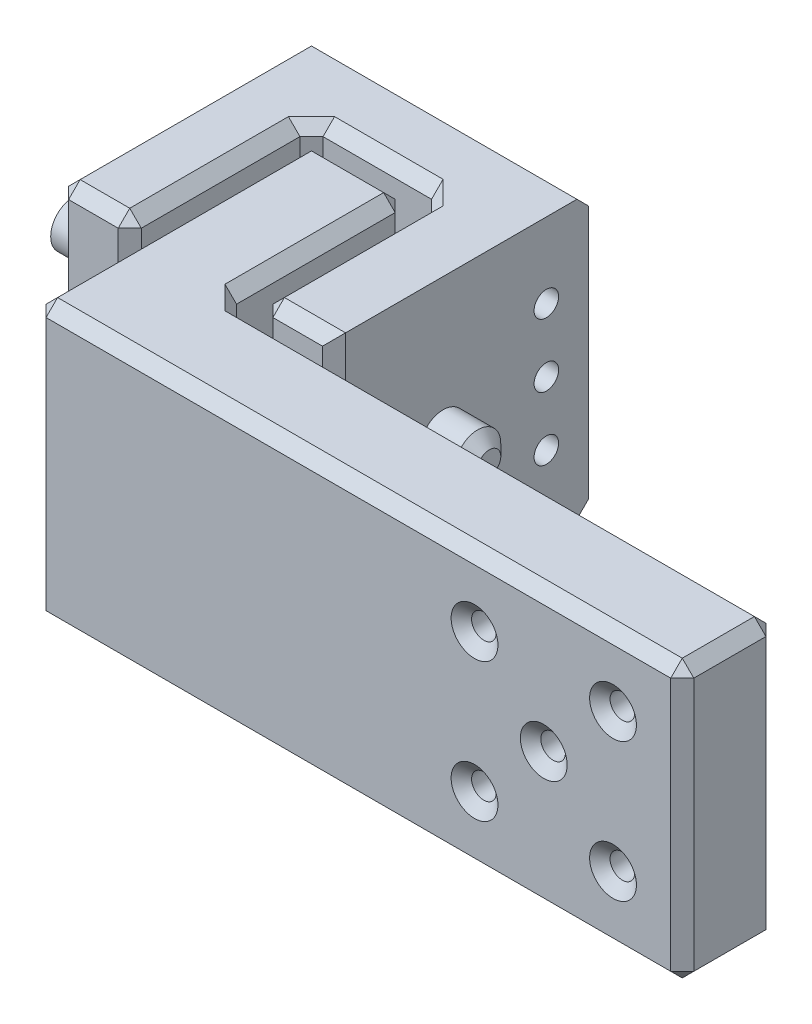
SolidWorks part; units mm, degrees
note: The reader was unsure of these and kept them because the rebuilt part matched: shared geometry of "Sketch7<2>".
ref_plane "Front Plane" through (0, 0, 0) normal (0, 0, 1) x (1, 0, 0)
ref_plane "Top Plane" through (0, 0, 0) normal (0, 1, 0) x (1, 0, 0)
ref_plane "Right Plane" through (0, 0, 0) normal (1, 0, 0) x (0, 0, -1)
sketch "Sketch1" plane through (0, 0, 0) normal (0, 1, 0) x (1, 0, 0)
  line L0 (0, 0) -> (0, 50)
  line L1 (0, 50) -> (36.2, 50)
  line L2 (36.2, 50) -> (36.2, 0)
  line L3 (36.2, 0) -> (56.2, 0)
  line L4 (56.2, 0) -> (56.2, 70)
  line L5 (56.2, 70) -> (-20, 70)
  line L6 (-20, 70) -> (-20, 0)
  line L7 (-20, 0) -> (0, 0)
  line L8 (31.2, 45) -> (5, 45)
  line L9 (5, 45) -> (5, -31.2)
  line L10 (5, -31.2) -> (183.2, -31.2)
  line L11 (183.2, -31.2) -> (183.2, -5)
  line L12 (183.2, -5) -> (31.2, -5)
  line L13 (31.2, -5) -> (31.2, 45)
  dimension "D1" = 5
  dimension "D2" = 5
  dimension "D3" = 5
  dimension "D4" = 5
  dimension "D5" = 20
  dimension "D6" = 20
  dimension "D7" = 20
  dimension "D8" = 76.2
  dimension "D9" = 76.2
  dimension "D10" = 127
extrude "Boss-Extrude1" add sketch "Sketch1" along normal blind 76.2
ref_plane "Plane1" through (0, 0, -45) normal (0, 0, -1) x (-1, 0, 0)
ref_plane "Plane2" through (0, 0, 0) normal (0, 0, 1) x (1, 0, 0)
sketch "Sketch3" plane through (-20, 0, 0) normal (-1, 0, 0) x (0, 0, 1)
  line L0 (0, 38.1) -> (-70, 38.1) construction
  line L3 (0, 76.2) -> (0, 0) construction
  line L6 (-70, 76.2) -> (-70, 0) construction
  line L8 (-45, 76.2) -> (-45, 0) construction
  circle A0 centre (-30, 38.1) radius 6.35
  point P7 (0, 0)
  point P8 (0, 0)
  point P9 (0, 0)
  point P10 (0, 0)
  dimension "D1" = 12.7
  dimension "D2" = 15
extrude "Cut-Extrude1" cut sketch "Sketch3" against normal through all both and the other way through all contours A0
chamfer "Chamfer1" distance 6.35 angle 45 1 edges at (-20, 38.1, -36.35)
chamfer "Chamfer2" distance 3.175 angle 45 20 edges at (31.2, 38.1, -23.65) (5, 38.1, -36.35) (183.2, 38.1, 5) (183.2, 76.2, 18.1) (183.2, 38.1, 31.2) (183.2, 0, 18.1) (18.1, 0, -45) (31.2, 0, -20) (107.2, 0, 5) (31.2, 38.1, 5) (94.1, 0, 31.2) (5, 0, -6.9) (5, 38.1, 31.2) (94.1, 76.2, 31.2) (5, 76.2, -6.9) (107.2, 76.2, 5) (31.2, 76.2, -20) (31.2, 38.1, -45) (18.1, 76.2, -45) (5, 38.1, -45)
chamfer "Chamfer3" distance 3.175 angle 45 1 edges at (36.2, 38.1, -36.35)
chamfer "Chamfer4" distance 3.175 angle 45 23 edges at (18.1, 0, -50) (46.2, 76.2, 0) (56.2, 76.2, -35) (56.2, 38.1, 0) (56.2, 0, -35) (46.2, 0, 0) (36.2, 0, -25) (36.2, 38.1, 0) (0, 38.1, -50) (-20, 38.1, -70) (-20, 0, -35) (0, 0, -25) (-10, 0, 0) (0, 38.1, 0) (-20, 38.1, 0) (36.2, 76.2, -25) (18.1, 76.2, -50) (0, 76.2, -25) (-10, 76.2, 0) (-20, 76.2, -35) (36.2, 38.1, -50) (18.1, 0, -70) (18.1, 76.2, -70)
sketch "Sketch4" plane through (0, 0, 31.2) normal (0, 0, 1) x (1, 0, 0)
  line L0 (180.025, 73.025) -> (8.175, 73.025) construction
  line L1 (110.175, 3.175) -> (180.025, 3.175) construction
  line L2 (110.175, 3.175) -> (110.175, 73.025) construction
  line L3 (110.175, 73.025) -> (180.025, 73.025) construction
  line L4 (180.025, 3.175) -> (180.025, 73.025) construction
  line L5 (110.175, 3.175) -> (180.025, 73.025) construction
  line L6 (110.175, 73.025) -> (180.025, 3.175) construction
  line L7 (180.025, 3.175) -> (180.025, 73.025) construction
  line L8 (8.175, 3.175) -> (180.025, 3.175) construction
  line L10 (126.05, 19.05) -> (164.15, 19.05) construction
  line L11 (126.05, 19.05) -> (126.05, 57.15) construction
  line L12 (126.05, 57.15) -> (164.15, 57.15) construction
  line L13 (164.15, 19.05) -> (164.15, 57.15) construction
  line L14 (126.05, 19.05) -> (164.15, 57.15) construction
  line L15 (126.05, 57.15) -> (164.15, 19.05) construction
  point P0 (145.1, 38.1)
  point P11 (145.1, 38.1)
  point P17 (126.05, 57.15)
  point P18 (164.15, 57.15)
  point P19 (164.15, 19.05)
  point P20 (126.05, 19.05)
  dimension "D1" = 38.1
hole_wizard "CSK for 1/4 Flat Head Machine Screw (100)1" positions "Sketch4" profile "Sketch6" countersink size "1/4" standard "ANSI Inch"
sketch "Sketch6" plane through (126.05, 19.05, 31.2) normal (1, 0, 0) x (0, -1, 0)
  line L0 (0, 0) -> (0, 28.2298)
  line L1 (0, 28.2298) -> (3.3782, 26.2)
  line L2 (3.3782, 26.2) -> (3.3782, 2.5682)
  line L3 (3.3782, 2.5682) -> (6.4389, 0)
  line L5 (6.4389, 0) -> (0, 0)
  line L6 (-3.3782, 2.5682) -> (-6.4389, 0) construction
  line L10 (0, 28.2298) -> (-3.3782, 26.2) construction
  line L11 (0, -6.35) -> (0, 107.95) construction
  dimension "Hole Dia." = 6.7564
  dimension "Hole Depth" = 26.2
  dimension "Near C'Sink Dia." = 12.8778
  dimension "Near C'Sink Angle" = 100
  dimension "Drill Angle" = 118
sketch "Sketch7" plane through (-20, 0, 0) normal (-1, 0, 0) x (0, 0, 1)
  circle A0 centre (-30, 38.1) radius 6.35
  circle A1 centre (-30, 38.1) radius 6.35 construction
extrude "Boss-Extrude2" add sketch "Sketch7" against normal blind 88.9 separate body
extrude "Boss-Extrude3" add sketch "Sketch7<2>" along normal blind 25.4
sketch "Sketch7<2>" plane through (-20, 0, 0) normal (-1, 0, 0) x (0, 0, 1) same geometry as "Sketch7"
sketch "Sketch8" plane through (-20, 0, 0) normal (-1, 0, 0) x (0, 0, 1)
  line L0 (-66.825, 3.175) -> (-3.175, 3.175) construction
  line L1 (-66.825, 73.025) -> (-50, 73.025) construction
  line L2 (-66.825, 73.025) -> (-66.825, 3.175) construction
  line L3 (-66.825, 3.175) -> (-50, 3.175) construction
  line L4 (-50, 73.025) -> (-50, 3.175) construction
  line L5 (-50, 73.025) -> (-50, 3.175) construction
  line L7 (-58.4125, 38.1) -> (-58.4125, 20.6375) construction
  line L8 (-58.4125, 20.6375) -> (-58.4125, 3.175) construction
  line L9 (-58.4125, 38.1) -> (-58.4125, 55.5625) construction
  line L11 (-58.4125, 55.5625) -> (-58.4125, 73.025) construction
  point P11 (-58.4125, 38.1)
  point P15 (-58.4125, 20.6375)
  point P30 (-58.4125, 55.5625)
  point P33 (-58.4125, 38.1)
  point P36 (-58.4125, 20.6375)
hole_wizard "CSK for 1/4 Flat Head Machine Screw (100)2" positions "Sketch8" profile "Sketch9" countersink size "1/4" standard "ANSI Inch"
sketch "Sketch9" plane through (-20, 20.6375, -58.4125) normal (0, 1, 0) x (0, 0, 1)
  line L0 (0, 0) -> (0, 78.2298)
  line L1 (0, 78.2298) -> (3.3782, 76.2)
  line L2 (3.3782, 76.2) -> (3.3782, 2.5682)
  line L3 (3.3782, 2.5682) -> (6.4389, 0)
  line L5 (6.4389, 0) -> (0, 0)
  line L6 (-3.3782, 2.5682) -> (-6.4389, 0) construction
  line L10 (0, 78.2298) -> (-3.3782, 76.2) construction
  line L11 (0, -6.35) -> (0, 107.95) construction
  dimension "Hole Dia." = 6.7564
  dimension "Hole Depth" = 76.2
  dimension "Near C'Sink Dia." = 12.8778
  dimension "Near C'Sink Angle" = 100
  dimension "Drill Angle" = 118
chamfer "Chamfer5" distance 3.175 angle 45 1 edges at (68.9, 38.1, -23.65)
